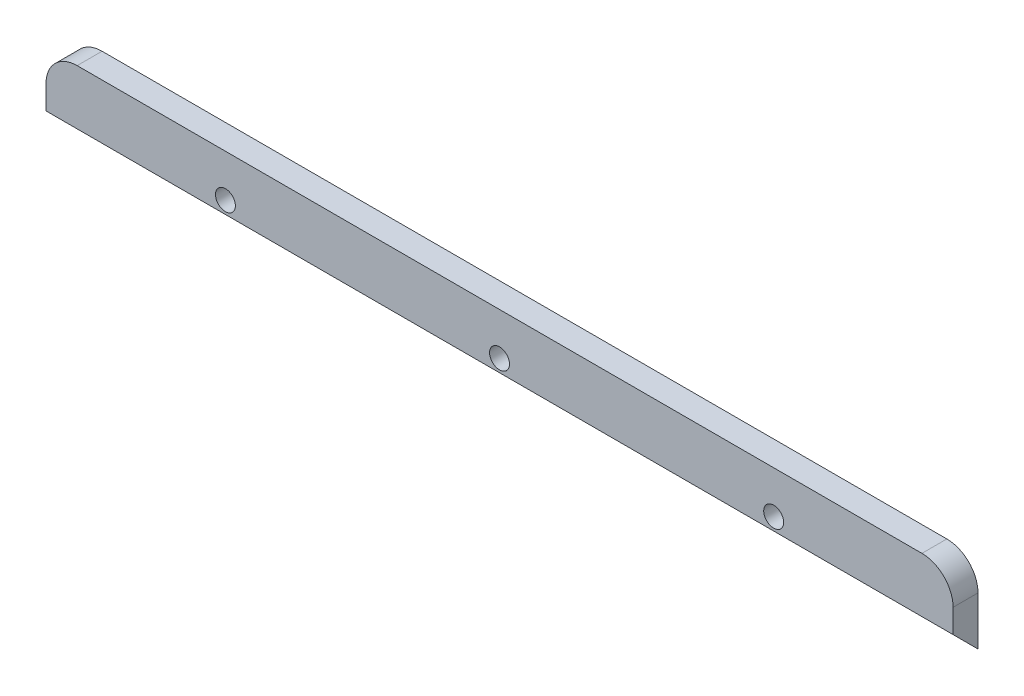
SolidWorks part; units mm, degrees
material "6061-T6 (SS)"
ref_plane "Front Plane" through (0, 0, 0) normal (0, 0, 1) x (1, 0, 0)
ref_plane "Top Plane" through (0, 0, 0) normal (0, 1, 0) x (1, 0, 0)
ref_plane "Right Plane" through (0, 0, 0) normal (1, 0, 0) x (0, 0, -1)
sketch "Sketch1" plane through (0, 0, 0) normal (1, 0, 0) x (0, 0, -1)
  line L0 (-3.0983, 0) -> (1.226, 0) construction
  line L1 (0, -3.2) -> (-2, -1.2)
  line L2 (0, -3.2) -> (0, 3.2)
  line L4 (-2, -1.2) -> (-2, 3.2)
  line L5 (-2, 3.2) -> (0, 3.2)
  dimension "D1" = 2
  dimension "D2" = 45
  dimension "D3" = 6.4
extrude "Boss-Extrude1" add sketch "Sketch1" along normal mid plane 72.8
sketch "Sketch4" [suppressed] plane through (0, 0, 0) normal (0, 0, 1) x (1, 0, 0)
  line L1 (7.5, 1.5) -> (-7.5, 1.5)
  line L2 (7.5, 1.5) -> (7.5, -3.2)
  line L3 (7.5, -3.2) -> (-7.5, -3.2)
  line L4 (-7.5, 1.5) -> (-7.5, -3.2)
  line L5 (0, 7.7759) -> (0, -8.8374) construction
  line L8 (-7.5, -3.2) -> (-7.5, 0.8) construction
  dimension "D1" = 4.7
hole_wizard "M2x0.4 Tapped Hole1" positions "Sketch2" profile "Sketch3" tap size "M2x0.4" standard "ANSI Metric" end condition through all
sketch "Sketch2" plane through (0, 0, 2) normal (0, 0, 1) x (1, 0, 0)
  circle A0 centre (-22, -0.2) radius 1.2
  circle A1 centre (-22, -0.2) radius 1.2 construction
  circle A2 centre (22, -0.2) radius 1.2
  circle A3 centre (22, -0.2) radius 1.2 construction
  point P0 (22, -0.2)
  point P2 (0, -0.2)
  point P5 (-22, -0.2)
sketch "Sketch3" plane through (22, -0.2, 2) normal (1, 0, 0) x (0, -1, 0)
  line L0 (0, 0) -> (0, 2)
  line L1 (0, 2) -> (0.8, 2)
  line L2 (0.8, 2) -> (0.8, 0)
  line L5 (0.8, 0) -> (0, 0)
  line L11 (0, -6.35) -> (0, 107.95) construction
  dimension "Thru Tap Drill Dia." = 1.6
  dimension "Thru Tap Drill Depth" = 2
cosmetic thread "Hole Thread1"
cosmetic thread "Hole Thread2"
cosmetic thread "Hole Thread3"
extrude "Cut-Extrude4" [suppressed] cut sketch "Sketch4" along normal through all
fillet "Fillet3" radius 2.5 2 edges at (-36.4, 3.2, 1) (36.4, 3.2, 1)
